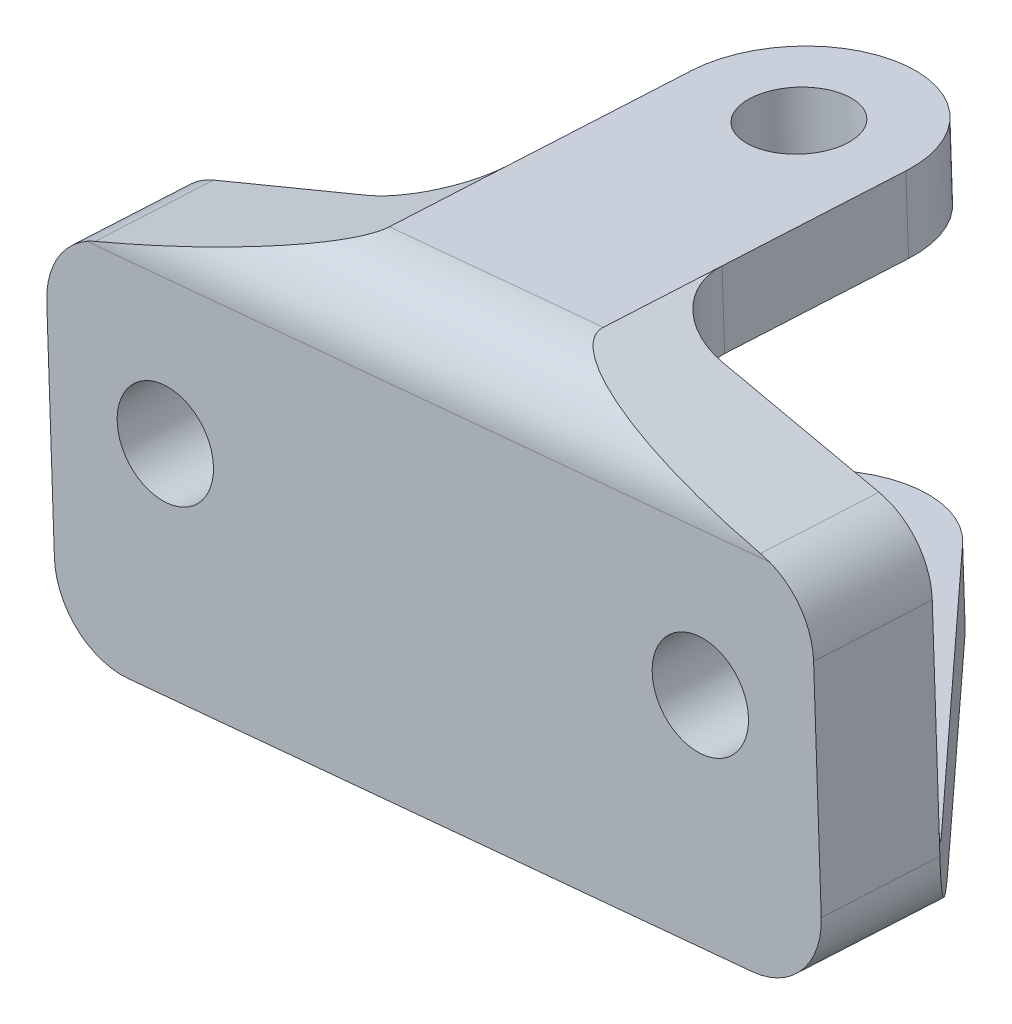
SolidWorks part; units mm, degrees
material "7075-T6 (SN)"
ref_plane "正面" through (0, 0, 0) normal (0, 0, 1) x (1, 0, 0)
ref_plane "平面" through (0, 0, 0) normal (0, 1, 0) x (1, 0, 0)
ref_plane "右側面" through (0, 0, 0) normal (1, 0, 0) x (0, 0, -1)
sketch3d "3Dｽｹｯﾁ1"
  line L3 (666.6951, 372.5, 572.5415) -> (797.0383, 324.8965, 186.598)
  line L8 (710.5842, 360.3192, 610.6731) -> (635.9213, 353.674, 611.0213)
  line L9 (698.179, 387.2876, 609.2597) -> (710.5842, 360.3192, 610.6731)
  line L10 (643.3962, 382.4117, 609.5152) -> (698.179, 387.2876, 609.2597)
  line L11 (635.9213, 353.674, 611.0213) -> (634.3234, 371.5784, 610.083)
  line L12 (666.6951, 372.5, 572.5415) -> (354.3522, 303.2688, 280.0587)
  line L13 (700, 0, 605) -> (657.4578, 475.8142, 563.539)
  circle A2 centre (689.1062, 376.4542, 609.8275) radius 4.05
  circle A4 centre (644.2839, 372.4649, 610.0365) radius 4.05
  arc A6 (634.3234, 371.5784, 610.083) -> (643.3962, 382.4117, 609.5152) centre (644.2839, 372.4649, 610.0365) ccw
  point P7 (689.1062, 376.2422, 605.783)
  point P12 (644.2839, 372.2529, 605.9921)
  point P17 (644.2839, 371.9415, 600.0502)
ref_plane "平面1" through (0, 32.9033, 627.8322) normal (0, -0.0523, -0.9986) x (-1, 0, 0)
sketch "ｽｹｯﾁ2" plane through (0, 32.9033, 627.8322) normal (0, -0.0523, -0.9986) x (-1, 0, 0)
  line L0 (-689.1062, 344.0224) -> (-644.2839, 340.0276) construction
  line L1 (-697.0423, 364.8089) -> (-700.5932, 324.9669)
  line L2 (-700.5932, 324.9669) -> (-636.3479, 319.241)
  line L3 (-636.3479, 319.241) -> (-632.7969, 359.0831)
  line L4 (-632.7969, 359.0831) -> (-697.0423, 364.8089)
  circle A0 centre (-689.1062, 344.0224) radius 9.75 construction
  circle A1 centre (-644.2839, 340.0276) radius 9.75 construction
  circle A2 centre (-644.2839, 340.0276) radius 4.05
  circle A3 centre (-689.1062, 344.0224) radius 4.05
  dimension "D1" = 8.1
  dimension "D2" = 8.1
  dimension "D3" = 19.5
  dimension "D4" = 19.5
  dimension "D5" = 40
  dimension "D6" = 20
extrude "ﾎﾞｽ - 押し出し1" add sketch "ｽｹｯﾁ2" along normal blind 50
sketch "ｽｹｯﾁ4" plane through (0, 32.9033, 627.8322) normal (0, 0.0523, 0.9986) x (1, 0, 0)
  line L0 (636.1703, 321.2331) -> (700.4157, 326.959) construction
  line L1 (710.5842, 327.8652) -> (635.9213, 321.2109) construction
  line L2 (697.0423, 364.8089) -> (700.5932, 324.9669) construction
  line L3 (636.3479, 319.241) -> (632.7969, 359.0831) construction
sketch "ｽｹｯﾁ5" plane through (723.8065, 64.4208, -3.3762) normal (0.9961, 0.0887, -0.0046) x (-0.0046, -0.0004, -1)
  line L0 (-608.1435, 296.0951) -> (-567.6985, 293.9838)
  line L1 (-614.1033, 295.9055) -> (-564.1712, 293.299) construction
  line L2 (-567.6985, 293.9838) -> (-567.3858, 299.9757)
  line L3 (-567.3858, 299.9757) -> (-597.8443, 301.5657)
  line L4 (-597.8443, 301.5657) -> (-596.6453, 324.5344)
  line L5 (-596.6453, 324.5344) -> (-566.1868, 322.9444)
  line L6 (-566.1868, 322.9444) -> (-565.874, 328.9363)
  line L7 (-565.874, 328.9363) -> (-606.3189, 331.0475)
  line L14 (-564.2755, 291.3018) -> (-614.2075, 293.9083) construction
  line L15 (-574.8618, 329.4054) -> (-576.6863, 294.453) construction
  line L16 (-562.1903, 331.2474) -> (-564.2755, 291.3018) construction
  line L18 (-587.2584, 312.5287) -> (-564.2897, 311.3297) construction
  line L35 (-606.3189, 331.0475) -> (-626.0453, 332.0773)
  line L36 (-626.0453, 332.0773) -> (-625.405, 344.344)
  line L37 (-625.405, 344.344) -> (-551.556, 340.489)
  line L38 (-551.556, 340.489) -> (-554.6576, 281.0723)
  line L39 (-554.6576, 281.0723) -> (-628.5066, 284.9273)
  line L40 (-628.5066, 284.9273) -> (-628.5066, 296.9798)
  line L41 (-628.5066, 296.9798) -> (-608.1435, 296.0951)
  arc A0 (-565.874, 328.9363) -> (-583.8495, 329.8746) centre (-574.8618, 329.4054) ccw construction
  point P2 (-574.1577, 293.8203)
  point P21 (-575.774, 311.9292)
  point P30 (-575.774, 311.9292)
  dimension "D6" = 9
  dimension "D1" = 35
  dimension "D2" = 23
  dimension "D3" = 23
  dimension "D4" = 6
  dimension "D7" = 10
extrude "ｶｯﾄ - 押し出し1" cut sketch "ｽｹｯﾁ5" against normal blind 100
sketch "ｽｹｯﾁ6" plane through (723.8065, 64.4208, -3.3762) normal (0.9961, 0.0887, -0.0046) x (-0.0046, -0.0004, -1)
  line L0 (-606.3189, 331.0475) -> (-608.1435, 296.0951)
  line L1 (-567.6985, 293.9838) -> (-608.1435, 296.0951) construction
  line L2 (-612.2527, 331.3573) -> (-565.874, 328.9363) construction
  line L4 (-608.1435, 296.0951) -> (-619.733, 290.9533)
  line L5 (-619.733, 290.9533) -> (-617.7242, 336.8784)
  line L6 (-617.7242, 336.8784) -> (-606.3189, 331.0475)
  line L7 (-596.6453, 324.5344) -> (-597.8443, 301.5657) construction
  dimension "D1" = 10
extrude "ｶｯﾄ - 押し出し2" cut sketch "ｽｹｯﾁ6" against normal blind 100
sketch "ｽｹｯﾁ7" plane through (-26.5423, 297.4015, -15.5862) normal (-0.0888, 0.9947, -0.0521) x (0.9961, 0.0887, -0.0046)
  circle A0 centre (694.4255, -591.252) radius 4.05
  circle A1 centre (694.4255, -591.252) radius 9 construction
  dimension "D1" = 8.1
  dimension "D2" = 18
extrude "ｶｯﾄ - 押し出し3" cut sketch "ｽｹｯﾁ7" against normal blind 100
sketch "ｽｹｯﾁ8" plane through (-26.5423, 297.4015, -15.5862) normal (-0.0888, 0.9947, -0.0521) x (0.9961, 0.0887, -0.0046)
  line L0 (662.1755, -612.752) -> (726.6755, -612.752) construction
  line L1 (662.1755, -622.752) -> (662.1755, -582.252) construction
  line L2 (726.6755, -622.752) -> (726.6755, -582.252) construction
  line L3 (662.1755, -622.752) -> (726.6755, -622.752) construction
  line L4 (653.0838, -612.752) -> (685.4255, -612.752)
  line L5 (685.4255, -612.752) -> (685.4255, -591.2626)
  line L6 (662.1755, -582.252) -> (726.6755, -582.252) construction
  line L7 (732.6545, -612.752) -> (703.4255, -612.752)
  line L8 (703.4255, -612.752) -> (703.4255, -591.252)
  line L9 (732.6545, -612.752) -> (732.6545, -571.4473)
  line L10 (732.6545, -571.4473) -> (653.0838, -571.4473)
  line L11 (653.0838, -571.4473) -> (653.0838, -612.752)
  arc A0 (685.4255, -591.2626) -> (703.4255, -591.252) centre (694.4255, -591.252) cw
  dimension "D2" = 18
  dimension "D1" = 10
extrude "ｶｯﾄ - 押し出し6" cut sketch "ｽｹｯﾁ8" against normal blind 20
sketch "ｽｹｯﾁ9" plane through (-23.9678, 268.5556, -14.0744) normal (-0.0888, 0.9947, -0.0521) x (0.9961, 0.0887, -0.0046)
  line L0 (726.6755, -612.752) -> (726.6755, -582.252)
  line L1 (726.6755, -582.252) -> (662.1755, -582.252)
  line L2 (662.1755, -582.252) -> (662.1755, -612.752)
  line L3 (662.1755, -612.752) -> (687.8308, -585.1274)
  line L4 (726.6755, -612.752) -> (701.0201, -585.1274)
  arc A0 (687.8308, -585.1274) -> (701.0201, -585.1274) centre (694.4255, -591.252) cw
  line M9 (726.6755, -612.752) -> (726.6755, -582.252)
  line M10 (726.6755, -582.252) -> (662.1755, -582.252)
  line M11 (662.1755, -582.252) -> (662.1755, -612.752)
extrude "ｶｯﾄ - 押し出し7" cut sketch "ｽｹｯﾁ9" against normal blind 20 contours A0 L4 M10 M9 | L3 A0 L1 M11 region at (690.3455, 363.1339, 574.1561) region at (645.0864, 359.1057, 574.3673)
sketch "ｽｹｯﾁ10" plane through (0, 32.069, 611.9122) normal (0, -0.0523, -0.9986) x (-1, 0, 0)
  line L0 (-674.106, 360.2548) -> (-697.8856, 355.3464)
  line L1 (-697.2642, 362.3188) -> (-699.8386, 333.4333) construction
  line L2 (-697.8856, 355.3464) -> (-697.2642, 362.3188)
  line L3 (-674.106, 360.2548) -> (-697.2642, 362.3188) construction
  line L4 (-697.2642, 362.3188) -> (-674.106, 360.2548)
  line L5 (-656.1771, 358.6569) -> (-633.6427, 349.5929)
  line L6 (-633.0189, 356.5929) -> (-635.5933, 327.7074) construction
  line L7 (-633.6427, 349.5929) -> (-633.0189, 356.5929)
  line L8 (-633.0189, 356.5929) -> (-656.1771, 358.6569)
  dimension "D1" = 7
  dimension "D2" = 7
extrude "ｶｯﾄ - 押し出し8" cut sketch "ｽｹｯﾁ10" against normal blind 20
sketch "ｽｹｯﾁ11" plane through (0, 32.069, 611.9122) normal (0, -0.0523, -0.9986) x (-1, 0, 0)
  circle A0 centre (-689.1062, 344.0224) radius 9
  circle A1 centre (-644.2839, 340.0276) radius 9
  dimension "D1" = 18
  dimension "D2" = 18
fillet "ﾌｨﾚｯﾄ1" radius 6 4 edges at (633.6427, 381.4445, 598.6091) (697.8856, 387.1901, 598.308) (636.1259, 353.6208, 600.0673) (700.3713, 359.3389, 599.7676)
fillet "ﾌｨﾚｯﾄ2" radius 2 1 edges at (667.716, 362.1863, 594.6115)
fillet "ﾌｨﾚｯﾄ3" radius 6 1 edges at (665.1415, 391.5556, 603.0861)
fillet "ﾌｨﾚｯﾄ4" radius 6 3 edges at (656.4434, 387.2503, 593.298) (665.6742, 385.0641, 593.4125) (674.3723, 388.846, 593.2143)
sketch "ｽｹｯﾁ13" plane through (0, 32.069, 611.9122) normal (0, -0.0523, -0.9986) x (-1, 0, 0)
  circle A0 centre (-689.1062, 344.0224) radius 9.05
  circle A1 centre (-644.2839, 340.0276) radius 9.05
  dimension "D1" = 18.1
  dimension "D2" = 18.1
extrude "ｶｯﾄ - 押し出し9" cut sketch "ｽｹｯﾁ13" against normal blind 2
